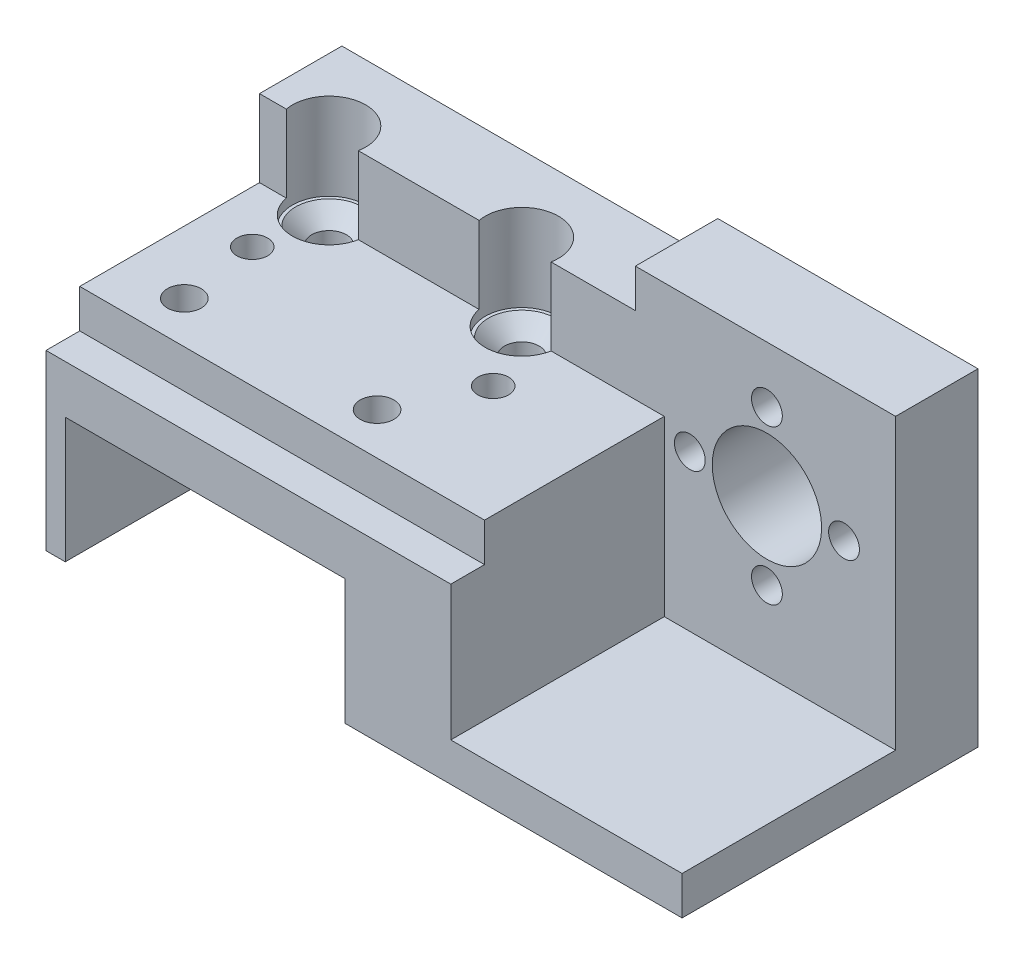
SolidWorks part; units mm, degrees
ref_plane "Front Plane" through (0, 0, 0) normal (0, 0, 1) x (1, 0, 0)
ref_plane "Top Plane" through (0, 0, 0) normal (0, 1, 0) x (1, 0, 0)
ref_plane "Right Plane" through (0, 0, 0) normal (1, 0, 0) x (0, 0, -1)
sketch "Croquis2" plane through (0, 0, 0) normal (0, 0, 1) x (1, 0, 0)
  line L0 (-42.15, -17.65) -> (-49.65, -17.65) construction
  line L1 (-42.15, -17.65) -> (-49.65, -17.65) construction
  line L2 (-49.65, -7.65) -> (-49.65, -17.65) construction
  line L3 (-49.65, -7.65) -> (-49.65, -17.65) construction
  line L5 (-52.65, -20.15) -> (13.35, -20.15)
  line L6 (-52.65, -20.15) -> (-52.65, 13.85)
  line L7 (-52.65, 13.85) -> (13.35, 13.85)
  line L8 (13.35, -20.15) -> (13.35, 13.85)
  line L9 (-50.65, -7.65) -> (-50.65, -7.15)
  line L10 (-21.65, -7.65) -> (-21.65, -17.65)
  line L11 (-21.65, -7.65) -> (-21.65, -20.15)
  line L13 (-50.65, -7.15) -> (-49.65, -7.15)
  line L14 (-21.65, -7.65) -> (-21.65, -7.15)
  line L15 (-21.65, -7.15) -> (-22.65, -7.15)
  line L16 (-50.65, -20.15) -> (-21.65, -20.15)
  line L17 (-30.45, -21.15) -> (-41.85, -21.15) construction
  line L18 (-49.65, -7.15) -> (-22.65, -7.15)
  line L19 (-49.65, -7.15) -> (-22.65, -7.15)
  line L28 (-50.65, -7.65) -> (-50.65, -17.65)
  line L29 (-50.65, -7.65) -> (-50.65, -20.15)
  circle A2 centre (0, 0) radius 5.67
  circle A3 centre (0, 0) radius 5.67
  circle A5 centre (0, 8) radius 1.3
  circle A6 centre (0, 8) radius 1.3
  circle A8 centre (8, 0) radius 1.3
  circle A9 centre (8, 0) radius 1.3
  circle A11 centre (0, -8) radius 1.3
  circle A12 centre (0, -8) radius 1.3
  circle A14 centre (-8, 0) radius 1.3
  circle A15 centre (-8, 0) radius 1.3
  circle M7 centre (0, 8) radius 1.6
  circle M8 centre (0, -8) radius 1.6
  circle M9 centre (8, 0) radius 1.6
  circle M10 centre (-8, 0) radius 1.6
  circle M12 centre (0, 0) radius 10.875
  dimension "D6" = 3
  dimension "D7" = 66
  dimension "D8" = 34
  dimension "D12" = 1
  dimension "D1" = 0.5
  dimension "D2" = 0.3
  dimension "D3" = 0.3
  dimension "D4" = 0.3
  dimension "D5" = 0.3
  dimension "D9" = 0.5
  dimension "D10" = 1
  dimension "D11" = 1
extrude "Saliente-Extruir1" add sketch "Croquis2" along normal offset from surface (30.7 mm away) 2 contours L29 L9 L13 L19 L15 L14 L11 L5 L8 L7 L6 M12 | A3 M12 M8 M10 M9 M7 region at (-20.3724, -1.2856, 0) region at (-10.5674, 0, 0)
sketch "Croquis4" plane through (0, 0, 30.7) normal (0, 0, 1) x (1, 0, 0)
  line L0 (-52.65, 13.85) -> (13.35, 13.85) construction
  line L1 (-10.65, 13.85) -> (13.35, 13.85)
  line L2 (-10.65, 13.85) -> (-10.65, -16.15)
  line L3 (-10.65, -16.15) -> (13.35, -16.15)
  line L4 (13.35, 13.85) -> (13.35, -16.15)
  line L5 (13.35, -20.15) -> (13.35, 13.85) construction
  line M9 (13.35, -20.15) -> (13.35, 13.85)
  line M10 (13.35, 13.85) -> (-52.65, 13.85)
  circle M13 centre (0, 0) radius 5.67
  circle M14 centre (0, -8) radius 1.6
  circle M15 centre (-8, 0) radius 1.6
  circle M16 centre (8, 0) radius 1.6
  circle M17 centre (0, 8) radius 1.6
  dimension "D1" = 24
  dimension "D2" = 30
extrude "Cortar-Extruir2" cut sketch "Croquis4" against normal offset from surface (22.7 mm away) 8 contours L2 L3 M9 M10 M13 M15 M17 M16 M14 region at (1.35, 13.4658, 30.7) up to face at (-27.9, -8.4, 0)
sketch "Croquis6" plane through (0, 0, 30.7) normal (0, 0, 1) x (1, 0, 0)
  line L0 (-30.15, -17.65) -> (-30.15, -13.15) construction
  line L1 (-21.65, -20.15) -> (-50.65, -20.15)
  line L2 (-21.65, -20.15) -> (-21.65, -7.15)
  line L3 (-21.65, -7.15) -> (-50.65, -7.15)
  line L4 (-50.65, -20.15) -> (-50.65, -7.15)
  line L5 (-30.15, -13.15) -> (-42.15, -13.15) construction
  line L6 (-42.15, -13.15) -> (-42.15, -17.65) construction
  line L7 (-29.65, -20.15) -> (-29.65, -12.65)
  line L8 (-29.65, -12.65) -> (-42.65, -12.65)
  line L9 (-42.65, -12.65) -> (-42.65, -20.15)
  line L10 (-29.65, -17.65) -> (-29.65, -12.65) construction
  line L11 (-42.65, -12.65) -> (-42.65, -17.65) construction
  dimension "D1" = 0.5
sketch "Croquis3" plane through (-52.65, 0, 0) normal (-1, 0, 0) x (0, 0, 1)
  line L0 (-2, -7.65) -> (32.7, -7.65) construction
  line L1 (20.85, 1.85) -> (8.55, 1.85)
  line L2 (20.85, 1.85) -> (20.85, 9.85)
  line L3 (20.85, 9.85) -> (8.55, 9.85)
  line L4 (8.55, 1.85) -> (8.55, 9.85)
  line L5 (0, -20.15) -> (0, 13.85) construction
  line L6 (30.7, 13.85) -> (30.7, -20.15) construction
  dimension "D1" = 8
  dimension "D2" = 12.3
  dimension "D3" = 9.5
  dimension "D4" = 9.85
  dimension "D5" = 8.55
extrude "Cortar-Extruir5" cut sketch "Croquis3" against normal blind 42
sketch "Croquis5" plane through (0, 13.85, 0) normal (0, 1, 0) x (1, 0, 0)
  line L0 (-10.65, -20.85) -> (-10.65, -8.55) construction
  line L1 (-52.65, -20.85) -> (-52.65, -8.55) construction
  line L2 (-52.65, -14.7) -> (-11.635, -14.7) construction
  line L5 (-52.65, -20.85) -> (-52.65, -8.55)
  circle A0 centre (-47.25, -14.7) radius 1.6
  circle A1 centre (-22.25, -14.7) radius 1.6
  point P15 (-52.65, -14.7)
  dimension "D3" = 3.2
  dimension "D1" = 11.6
  dimension "D2" = 25
extrude "Cortar-Extruir6" cut sketch "Croquis5" against normal through all contours L2 A0 | A0 L2 | A1 L2 | L2 A1 region at (-47.25, 13.85, 14.0209) region at (-22.25, 13.85, 14.0209) region at (-22.25, 13.85, 15.3791) region at (-47.25, 13.85, 15.3791)
sketch "Croquis7" plane through (0, 13.85, 0) normal (0, 1, 0) x (1, 0, 0)
  line L0 (-52.65, 0) -> (13.35, 0) construction
  line L1 (-52.65, -30.7) -> (-10.65, -30.7)
  line L2 (-52.65, -30.7) -> (-52.65, 0)
  line L3 (-52.65, 0) -> (-10.65, 0)
  line L4 (-10.65, -30.7) -> (-10.65, 0)
  line L5 (-52.65, -8.55) -> (-52.65, -20.85) construction
  line L6 (-52.65, -8.55) -> (-52.65, -20.85)
  line L8 (-52.65, -20.85) -> (-10.65, -20.85)
  line L9 (-52.65, -20.85) -> (-52.65, -30.7)
  line L10 (-52.65, -30.7) -> (-10.65, -30.7)
  line L11 (-10.65, -20.85) -> (-10.65, -30.7)
  line M3 (-10.65, -30.7) -> (-10.65, -8)
  line M6 (13.35, 0) -> (-52.65, 0)
  line M7 (-52.65, 0) -> (-52.65, -30.7)
  line M8 (-52.65, -30.7) -> (-10.65, -30.7)
  circle M15 centre (-47.25, -14.7) radius 1.6
  circle M16 centre (-22.25, -14.7) radius 1.6
extrude "Cortar-Extruir7" cut sketch "Croquis7" against normal up to surface (4 mm away) contours L2 L8 L4 M6 M7 M16 M15 region at (-31.592, 13.85, 10.345) up to face at (-47.25, 9.85, 16.3)
sketch "Croquis9" plane through (-10.65, 0, 0) normal (-1, 0, 0) x (0, 0, 1)
  line L4 (8, 9.85) -> (8, 13.85)
  line L5 (8, 13.85) -> (0, 13.85)
  line L6 (0, 13.85) -> (0, 9.85)
  line L7 (0, 9.85) -> (8, 9.85)
  line L8 (8, 9.85) -> (8, 13.85)
  line L9 (8, 13.85) -> (0, 13.85)
  line L10 (0, 13.85) -> (0, 9.85)
  line L11 (0, 9.85) -> (8, 9.85)
  dimension "D1" = 0
extrude "Saliente-Extruir4" add sketch "Croquis9" along normal blind 3
extrude "Cortar-Extruir8" cut sketch "Croquis7<3>" against normal up to surface (12 mm away) contours L8 M7 M8 M3 region at (-31.65, 13.85, 25.775) up to face at (-47.25, 1.85, 13.1)
sketch "Croquis7<3>" plane through (0, 13.85, 0) normal (0, 1, 0) x (1, 0, 0) same geometry as "Croquis7"
sketch "Croquis11" plane through (0, 1.85, 0) normal (0, 1, 0) x (1, 0, 0)
  line L1 (-47.25, -10.3121) -> (-51.05, -12.5061)
  line L2 (-51.05, -12.5061) -> (-51.05, -16.8939)
  line L3 (-51.05, -16.8939) -> (-47.25, -19.0879)
  line L4 (-47.25, -19.0879) -> (-43.45, -16.8939)
  line L5 (-43.45, -16.8939) -> (-43.45, -12.5061)
  line L6 (-43.45, -12.5061) -> (-47.25, -10.3121)
  line L7 (-22.25, -10.3121) -> (-26.05, -12.5061)
  line L8 (-26.05, -12.5061) -> (-26.05, -16.8939)
  line L9 (-26.05, -16.8939) -> (-22.25, -19.0879)
  line L10 (-22.25, -19.0879) -> (-18.45, -16.8939)
  line L11 (-18.45, -16.8939) -> (-18.45, -12.5061)
  line L12 (-18.45, -12.5061) -> (-22.25, -10.3121)
  circle A0 centre (-46.1299, -7.85) radius 1.5 construction
  circle A1 centre (-26.1299, -7.85) radius 1.5 construction
  circle A2 centre (-26.15, -22.85) radius 1.5 construction
  circle A3 centre (-46.15, -22.85) radius 1.5 construction
  circle A4 centre (-46.1299, -7.85) radius 1.5 construction
  circle A5 centre (-26.1299, -7.85) radius 1.5 construction
  circle A6 centre (-26.15, -22.85) radius 1.5 construction
  circle A7 centre (-46.15, -22.85) radius 1.5 construction
  circle A8 centre (-46.1299, -7.85) radius 3.8
  circle A9 centre (-26.1299, -7.85) radius 3.8
  circle A10 centre (-26.15, -22.85) radius 3.8
  circle A11 centre (-46.15, -22.85) radius 3.8
  circle A12 centre (-47.25, -14.7) radius 3.8 construction
  circle A13 centre (-22.25, -14.7) radius 3.8 construction
  circle A14 centre (-46.1299, -7.85) radius 1.75
  circle A15 centre (-26.1299, -7.85) radius 1.75
  circle A16 centre (-26.15, -22.85) radius 1.75
  circle A17 centre (-46.15, -22.85) radius 1.75
  circle M13 centre (-47.25, -14.7) radius 1.6
  circle M14 centre (-22.25, -14.7) radius 1.6
  line M18 (-10.65, -8.55) -> (-52.65, -8.55)
  dimension "D1" = 7.6
  dimension "D2" = 7.6
  dimension "D3" = 3.5
extrude "Cortar-Extruir9" cut sketch "Croquis11" against normal offset from surface (9 mm away) 1 from surface contours A14 A8 M18 | A14 A8 L1 L6 M18 | L1 A8 L6 | A14 M18 | A14 M18 | A15 A9 M18 | A15 M18 | A15 M18 | A15 A9 M18 region at (-46.8614, 1.85, 11.0938) region at (-46.0098, 1.85, 9.8058) region at (-26.4732, 1.85, 4.1542) region at (-26.1299, 1.85, 9.9873) region at (-46.4732, 1.85, 4.1542) region at (-46.1299, 1.85, 8.9831) region at (-46.1299, 1.85, 7.4676) region at (-26.1299, 1.85, 8.9831) region at (-26.1299, 1.85, 7.4676) up to face at (-47.25, 1.85, 13.1) offset beyond the face yes starting at face at (-25.65, 9.85, 5.5167)
extrude "Cortar-Extruir10" cut sketch "Croquis11<3>" against normal through all contours A14 M18 | A14 M18 | A15 M18 | A15 M18 | A16 | A17 region at (-46.1299, 1.85, 8.9831) region at (-46.1299, 1.85, 7.4676) region at (-26.1299, 1.85, 8.9831) region at (-26.1299, 1.85, 7.4676) region at (-26.15, 1.85, 22.85) region at (-46.15, 1.85, 22.85)
sketch "Croquis11<3>" plane through (0, 1.85, 0) normal (0, 1, 0) x (1, 0, 0) same geometry as "Croquis11"
extrude "Cortar-Extruir11" cut sketch "Croquis11<4>" along normal blind 4 and the other way through all from surface contours A8 L1 L2 L3 L4 L5 L6 M13 | L11 L12 L7 L8 L9 L10 M14 | L1 A8 L6 region at (-46.8614, 1.85, 11.0938) region at (-46.8317, 1.85, 11.6979) region at (-20.408, 1.85, 11.5096) starting at face at (-46.15, -7.15, 24.6)
sketch "Croquis11<4>" plane through (0, 1.85, 0) normal (0, 1, 0) x (1, 0, 0) same geometry as "Croquis11"
hole_wizard "Avellanado para tornillo con cabeza avellanada de clavija hexagonal de M31" positions "Croquis16" profile "Croquis17" countersink size "M3" standard "DIN" end condition through all
sketch "Croquis16" plane through (0, 0.85, 0) normal (0, 1, 0) x (1, 0, 0)
  point P0 (-46.1299, -7.85)
  point P3 (-26.1299, -7.85)
sketch "Croquis17" plane through (-46.1299, 0.85, 7.85) normal (1, 0, 0) x (0, 0, 1)
  line L0 (0, 0) -> (0, 21)
  line L1 (0, 21) -> (1.8, 21)
  line L2 (1.8, 21) -> (1.8, 1.67)
  line L3 (1.8, 1.67) -> (3.47, 0)
  line L5 (3.47, 0) -> (0, 0)
  line L6 (-1.8, 1.67) -> (-3.47, 0) construction
  line L11 (0, -6.35) -> (0, 107.95) construction
  dimension "Diámetro de taladro hasta el siguiente" = 3.6
  dimension "Profundidad de taladro hasta el siguiente" = 21
  dimension "Diámetro de avellanado cercano" = 6.94
  dimension "Ángulo de avellanado cercano" = 90
sketch "Croquis18" plane through (0, 1.85, 0) normal (0, 1, 0) x (1, 0, 0)
  line L0 (-10.65, -8.55) -> (-10.65, -30.7) construction
  line L1 (-52.65, -30.7) -> (-10.65, -30.7)
  line L2 (-52.65, -30.7) -> (-52.65, -27.2)
  line L3 (-52.65, -27.2) -> (-10.65, -27.2)
  line L4 (-10.65, -30.7) -> (-10.65, -27.2)
  dimension "D1" = 3.5
extrude "Cortar-Extruir12" cut sketch "Croquis18" against normal blind 4
sketch "Croquis19" plane through (0, 0, 8) normal (0, 0, 1) x (1, 0, 0)
  line L6 (-10.65, 9.85) -> (-10.65, -16.15)
  line L7 (-10.65, -16.15) -> (13.35, -16.15)
  line L8 (13.35, -16.15) -> (13.35, 13.85)
  line L9 (13.35, 13.85) -> (-13.65, 13.85)
  line L10 (-13.65, 13.85) -> (-13.65, 9.85)
  line L11 (-13.65, 9.85) -> (-10.65, 9.85)
  line L12 (-10.65, 9.85) -> (-10.65, -16.15)
  line L13 (-10.65, -16.15) -> (13.35, -16.15)
  line L14 (13.35, -16.15) -> (13.35, 13.85)
  line L15 (13.35, 13.85) -> (-13.65, 13.85)
  line L16 (-13.65, 13.85) -> (-13.65, 9.85)
  line L17 (-13.65, 9.85) -> (-10.65, 9.85)
  circle A0 centre (0, 0) radius 5.67 construction
  circle A1 centre (0, -8) radius 1.6 construction
  circle A2 centre (8, 0) radius 1.6 construction
  circle A3 centre (0, 8) radius 1.6 construction
  circle A4 centre (-8, 0) radius 1.6 construction
  circle A5 centre (0, 0) radius 5.67
  circle A6 centre (0, -8) radius 1.6
  circle A7 centre (8, 0) radius 1.6
  circle A8 centre (0, 8) radius 1.6
  circle A9 centre (-8, 0) radius 1.6
  dimension "D1" = 0
extrude "Saliente-Extruir5" add sketch "Croquis19" along normal up to surface (0.55 mm away) up to face at (-16.5224, 5.85, 8.55)
